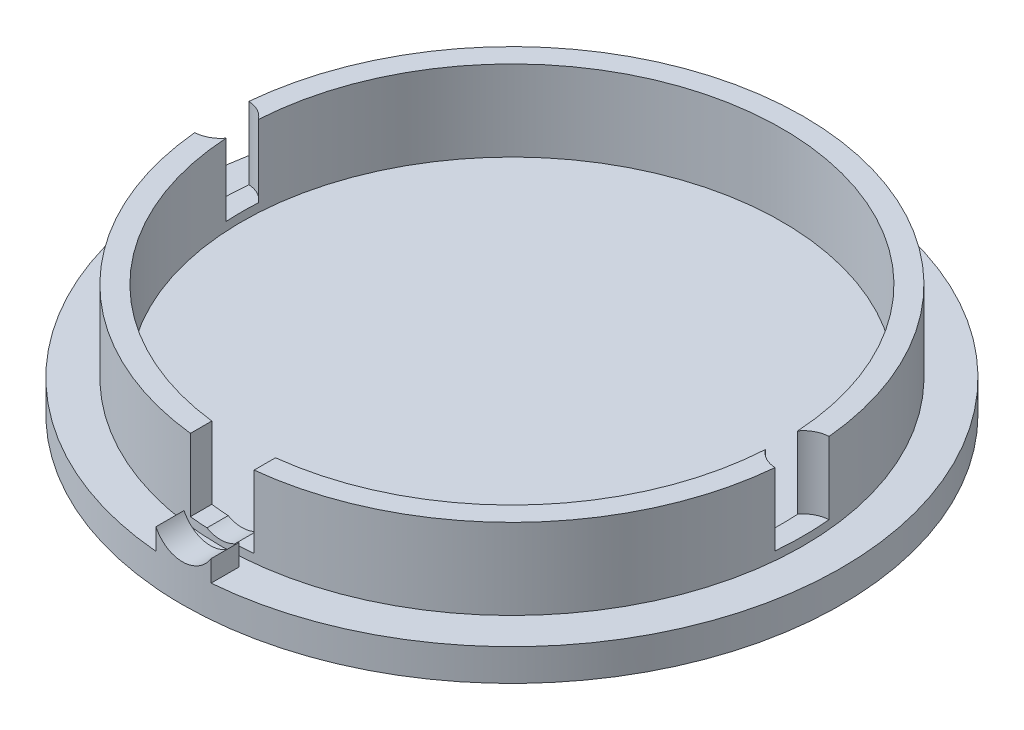
SolidWorks part; units mm, degrees
ref_plane "Front Plane" through (0, 0, 0) normal (0, 0, 1) x (1, 0, 0)
ref_plane "Top Plane" through (0, 0, 0) normal (0, 1, 0) x (1, 0, 0)
ref_plane "Right Plane" through (0, 0, 0) normal (1, 0, 0) x (0, 0, -1)
sketch "Sketch1" plane through (0, 0, 0) normal (0, 1, 0) x (1, 0, 0)
  circle A0 centre (0, 0) radius 31.06
  dimension "D1" = 62.12
extrude "Boss-Extrude1" add sketch "Sketch1" along normal blind 3
sketch "Sketch2" plane through (0, 3, 0) normal (0, 1, 0) x (1, 0, 0)
  circle A0 centre (0, 0) radius 27.46
  circle A1 centre (0, 0) radius 25.46
  circle A2 centre (0, 0) radius 31.06 construction
  dimension "D1" = 2
  dimension "D2" = 3.6
extrude "Boss-Extrude2" add sketch "Sketch2" along normal blind 7.6
sketch "Sketch4" plane through (0, 10.6, 0) normal (0, 1, 0) x (1, 0, 0)
  arc A0 (25.4144, -1.5226) -> (27.3416, -2.5472) centre (27.46, 0) ccw
  circle A1 centre (0, 0) radius 27.46 construction
  arc A2 (-27.3416, -2.5472) -> (-25.4144, -1.5226) centre (-27.46, 0) ccw
  circle A3 centre (0, 0) radius 25.46 construction
  arc A4 (-25.4144, 1.5226) -> (-25.4144, -1.5226) centre (0, 0) ccw
  arc A5 (-27.3416, 2.5472) -> (-27.3416, -2.5472) centre (0, 0) ccw
  arc A6 (25.4144, -1.5226) -> (25.4144, 1.5226) centre (0, 0) ccw
  arc A7 (27.3416, -2.5472) -> (27.3416, 2.5472) centre (0, 0) ccw
  arc A8 (-25.4144, 1.5226) -> (-27.3416, 2.5472) centre (-27.46, 0) ccw
  arc A9 (27.3416, 2.5472) -> (25.4144, 1.5226) centre (27.46, 0) ccw
  circle M1 centre (0, 0) radius 27.46
  circle M2 centre (0, 0) radius 25.46
  dimension "D1" = 5.1
  dimension "D2" = 5.1
extrude "Cut-Extrude1" cut sketch "Sketch4" against normal blind 6.8 contours A9 A0 M1 M2 | A4 A2 A5 A8 region at (26.5014, 10.6, 0)
sketch "Sketch5" plane through (0, 10.6, 0) normal (0, 1, 0) x (1, 0, 0)
  line L0 (0, -25.46) -> (0, -27.46)
  line L1 (3, -25.2826) -> (3, -27.2956)
  line L2 (-3, -25.2826) -> (-3, -27.2956)
  line L3 (3, -25.46) -> (3, -27.46) construction
  line L4 (-3, -25.46) -> (-3, -27.46) construction
  arc A0 (-25.4144, -1.5226) -> (25.4144, -1.5226) centre (0, 0) ccw construction
  arc A1 (-27.3416, -2.5472) -> (27.3416, -2.5472) centre (0, 0) ccw construction
  arc A3 (-3, -25.2826) -> (3, -25.2826) centre (0, 0) ccw
  arc A4 (-3, -27.2956) -> (3, -27.2956) centre (0, 0) ccw
  arc M2 (-27.3416, -2.5472) -> (27.3416, -2.5472) centre (0, 0) ccw
  arc M4 (25.4144, -1.5226) -> (-25.4144, -1.5226) centre (0, 0) cw
  dimension "D1" = 3
  dimension "D2" = 3
extrude "Cut-Extrude2" cut sketch "Sketch5" against normal blind 6.8 contours L2 L0 M4 M2 | L1 L0 M4 M2 region at (1.5016, 10.6, 26.403) region at (-1.5016, 10.6, 26.403)
sketch "Sketch7" plane through (0, 3, 0) normal (0, 1, 0) x (1, 0, 0)
  line L2 (2.6, -28.3014) -> (2.6, -30.951)
  line L3 (-2.6, -28.3014) -> (-2.6, -30.951)
  line L4 (3, -25.2826) -> (3, -27.2956) construction
  circle A0 centre (0, 0) radius 31.06 construction
  arc A1 (-2.6, -30.951) -> (2.6, -30.951) centre (0, 0) ccw
  arc A4 (-2.6, -28.3014) -> (2.6, -28.3014) centre (0, 0.0395) ccw
  dimension "D1" = 5.2
  dimension "D2" = 0.4
extrude "Boss-Extrude5" add sketch "Sketch7" along normal blind 7.6
ref_plane "Plane1" through (0, 0, 31.06) normal (0, 0, 1) x (1, 0, 0)
sketch "Sketch8" plane through (0, 0, 31.06) normal (0, 0, 1) x (1, 0, 0)
  line L0 (2.6, 10.6) -> (-2.6, 10.6) construction
  line L1 (2.6, 10.6) -> (-2.6, 10.6)
  line L2 (31.06, 3) -> (-31.06, 3) construction
  line L3 (2.6, 3) -> (-2.6, 3)
  line L4 (2.6, 10.6) -> (2.6, 3) construction
  line L5 (2.6, 10.6) -> (2.6, 3)
  line L6 (-2.6, 10.6) -> (-2.6, 3) construction
  line L7 (-2.6, 10.6) -> (-2.6, 3)
  line L8 (-2.6, 6.5) -> (2.6, 6.5)
  circle A0 centre (0, 6.5) radius 3
  dimension "D2" = 6
  dimension "D1" = 3.5
extrude "Cut-Extrude3" cut sketch "Sketch8" against normal blind 7.6 contours L7 A0 L5 L8 | L5 A0 L7 L8 | A0 L5 L1 L7 region at (0, 9.7737, 31.06) region at (0, 7.8162, 31.06) region at (0, 5.1838, 31.06)
